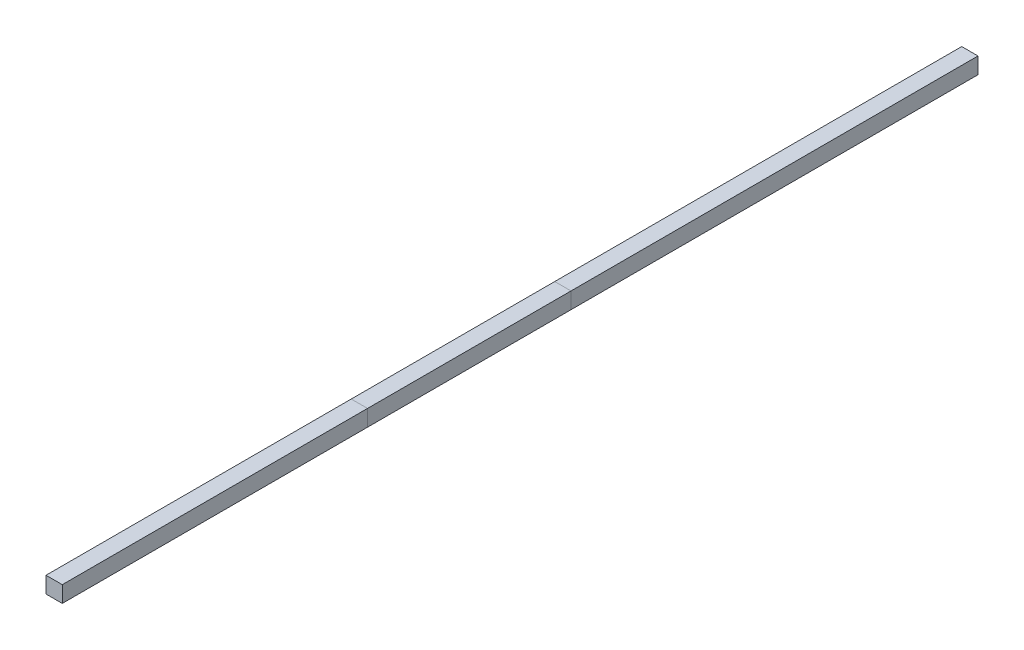
SolidWorks part; units mm, degrees
material "Stal stopowa"
ref_plane "Płaszczyzna przednia" through (0, 0, 0) normal (0, 0, 1) x (1, 0, 0)
ref_plane "Płaszczyzna górna" through (0, 0, 0) normal (0, 1, 0) x (1, 0, 0)
ref_plane "Płaszczyzna prawa" through (0, 0, 0) normal (1, 0, 0) x (0, 0, -1)
sketch "Szkic1" plane through (0, 0, 0) normal (0, 0, 1) x (1, 0, 0)
  line L1 (0, 0) -> (80, 0)
  line L2 (0, 0) -> (0, 80)
  line L3 (0, 80) -> (80, 80)
  line L4 (80, 0) -> (80, 80)
  dimension "D1" = 80
  dimension "D2" = 80
extrude "Dodanie-wyciągnięcie8" add sketch "Szkic1" along normal blind 2000
extrude "Dodanie-wyciągnięcie9" add sketch "Szkic1<12>" along normal blind 1000 from offset 2000 separate body
sketch "Szkic1<12>" plane through (0, 0, 0) normal (0, 0, 1) x (1, 0, 0) same geometry as "Szkic1"
extrude "Dodanie-wyciągnięcie10" add sketch "Szkic1<13>" along normal blind 1500 from offset 3000 separate body
sketch "Szkic1<13>" plane through (0, 0, 0) normal (0, 0, 1) x (1, 0, 0) same geometry as "Szkic1"
